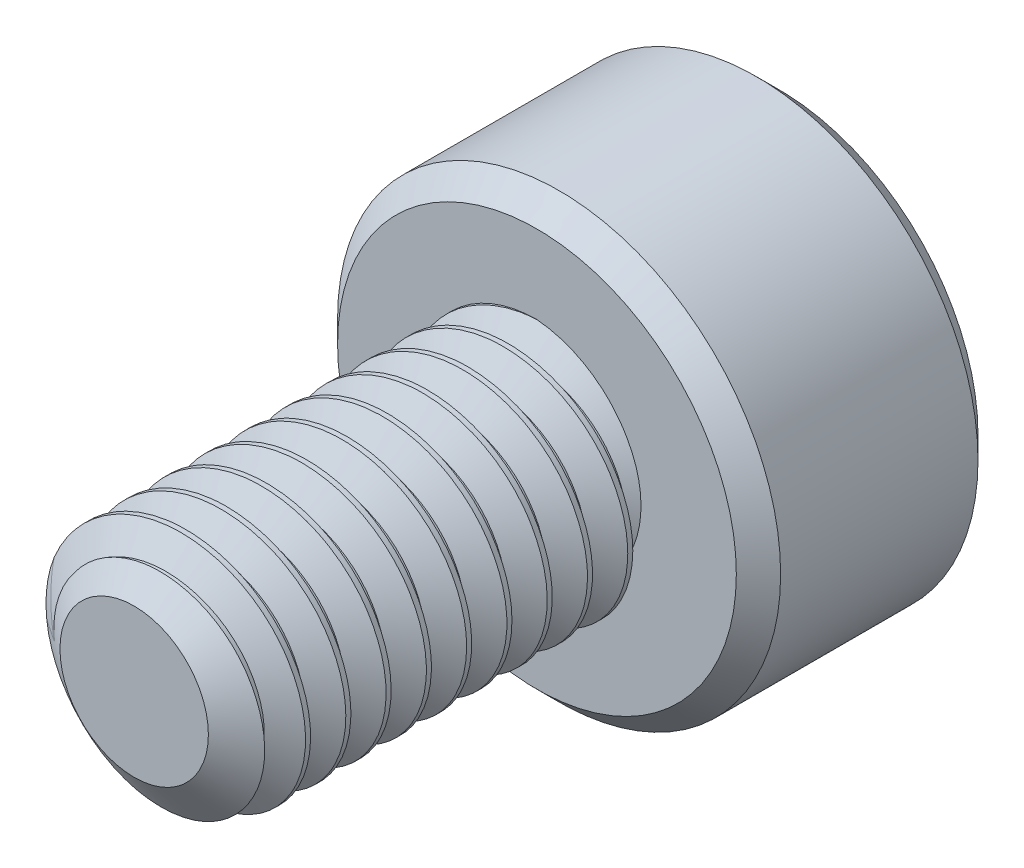
SolidWorks part; units mm, degrees
other "DetailItem1"
ref_plane "Front Plane" through (0, 0, 0) normal (0, 0, 1) x (1, 0, 0)
ref_plane "Top Plane" through (0, 0, 0) normal (0, 1, 0) x (1, 0, 0)
ref_plane "Right Plane" through (0, 0, 0) normal (1, 0, 0) x (0, 0, -1)
sketch "Sketch1" plane through (0, 0, 0) normal (0, 0, 1) x (1, 0, 0)
  circle A0 centre (0, 0) radius 1.5
  dimension "OD" = 3
extrude "Extrude1" add sketch "Sketch1" against normal blind 5
sketch "Sketch2" plane through (0, 0, 0) normal (0, 0, 1) x (1, 0, 0)
  circle A0 centre (0, 0) radius 1.5 construction
  circle A1 centre (0, 0) radius 1.5
curve "Helix/Spiral1" pitch 0.5 height 5.5 radius 1.5 centre (0, 0, 0) axis (0, 0, -1) start towards (0, 1, 0) parameters "pitch"=0.5
sketch "Sketch3" plane through (0, 0, 0) normal (1, 0, 0) x (0, 0, -1)
  line L0 (-0.4375, 1.5) -> (-0.25, 1.1752)
  line L1 (-0.25, 1.1752) -> (-0.1875, 1.1752)
  line L2 (-0.1875, 1.1752) -> (0, 1.5)
  line L3 (-0.4375, 1.5) -> (0, 1.5)
  line L4 (-0.2187, 1.5) -> (-0.2188, 1.1752) construction
  line L5 (-0.3438, 1.3376) -> (-0.0938, 1.3376) construction
  line L6 (0, 1.5) -> (0, -1.5) construction
  dimension "D1" = 0.0625
  dimension "D2" = 0.25
  dimension "D3" = 60
sweep "Cut-Sweep1" cut profiles "Sketch3" path "Helix/Spiral1" align with end faces yes
sketch "Sketch4" plane through (0, 0, 0) normal (1, 0, 0) x (0, 0, -1)
  line L0 (0.4053, 1.5) -> (0, 0.9212)
  line L1 (0, 0.9212) -> (0, 1.5)
  line L2 (0.4053, 1.5) -> (0, 1.5)
  line L3 (-0.4375, 1.5) -> (0, 1.5) construction
  line L4 (0, 0) -> (7.0209, 0) construction
  dimension "D1" = 55
  dimension "D2" = 0.254
revolve "Cut-Revolve1" cut sketch "Sketch4" angle 360 about L4
sketch "Sketch6" plane through (0, 0, -5) normal (0, 0, -1) x (-1, 0, 0)
  circle A0 centre (0, 0) radius 2.75
  dimension "head dia" = 5.5
extrude "Extrude2" add sketch "Sketch6" along normal blind 3
sketch "Sketch7" plane through (0, 0, -8) normal (0, 0, -1) x (-1, 0, 0)
  line L1 (0, 1.4434) -> (-1.25, 0.7217)
  line L2 (-1.25, 0.7217) -> (-1.25, -0.7217)
  line L3 (-1.25, -0.7217) -> (0, -1.4434)
  line L4 (0, -1.4434) -> (1.25, -0.7217)
  line L5 (1.25, -0.7217) -> (1.25, 0.7217)
  line L6 (1.25, 0.7217) -> (0, 1.4434)
  circle A0 centre (0, 0) radius 1.25 construction
  dimension "hex dia" = 2.5
extrude "Cut-Extrude1" cut sketch "Sketch7" against normal blind 1.875
sketch "Sketch8" plane through (0, 0, -8) normal (0, 0, -1) x (-1, 0, 0)
  circle A0 centre (0, 0) radius 1.4434
extrude "Cut-Extrude2" cut sketch "Sketch8" against normal through all draft 45
chamfer "Chamfer1" distance 0.275 angle 45 2 edges at (-2.75, 0, -8) (-2.75, 0, -5)
sketch "Sketch10" plane through (0, 0, -5) normal (0, 0, 1) x (1, 0, 0)
  circle A1 centre (0, 0) radius 1.5
  circle A2 centre (0, 0) radius 1.5
  dimension "D1" = 0
ref_plane "Plane1" through (0, 0, 0) normal (0, 0, 1) x (1, 0, 0)
extrude "partial thread" [suppressed] add sketch "Sketch10" along normal up to surface (4 mm away) separate body up to plane "Plane1"
chamfer "Chamfer2" [suppressed] distance 0.06 angle 45
combine bodies "Combine1" [suppressed] operation type add bodies to combine 107 108
sketch "Sketch9" plane through (0, 0, 0) normal (1, 0, 0) x (0, 0, -1)
  line L0 (0, 1.5) -> (0, -1.5) construction
  line L1 (1.25, 1.5) -> (1.25, -1.5) construction
  dimension "D1" = 1.25
equation "\"D3@Helix/Spiral1\" = \"screw length@Extrude1\"+\"pitch@Helix/Spiral1\""
equation "\"D1@Sketch3\" = \"pitch@Helix/Spiral1\"*.125"
equation "\"D2@Sketch3\" = \"pitch@Helix/Spiral1\"*.5"
equation "\"D1@Cut-Extrude1\" = \"hex dia@Sketch7\"*.75"
equation "\"D1@Chamfer1\" = \"head dia@Sketch6\"*.05"
equation "\"D1@Sketch9\" = \"pitch@Helix/Spiral1\"*2.5"
equation "\"D1@Chamfer2\"=\"OD@Sketch1\"*.02"
